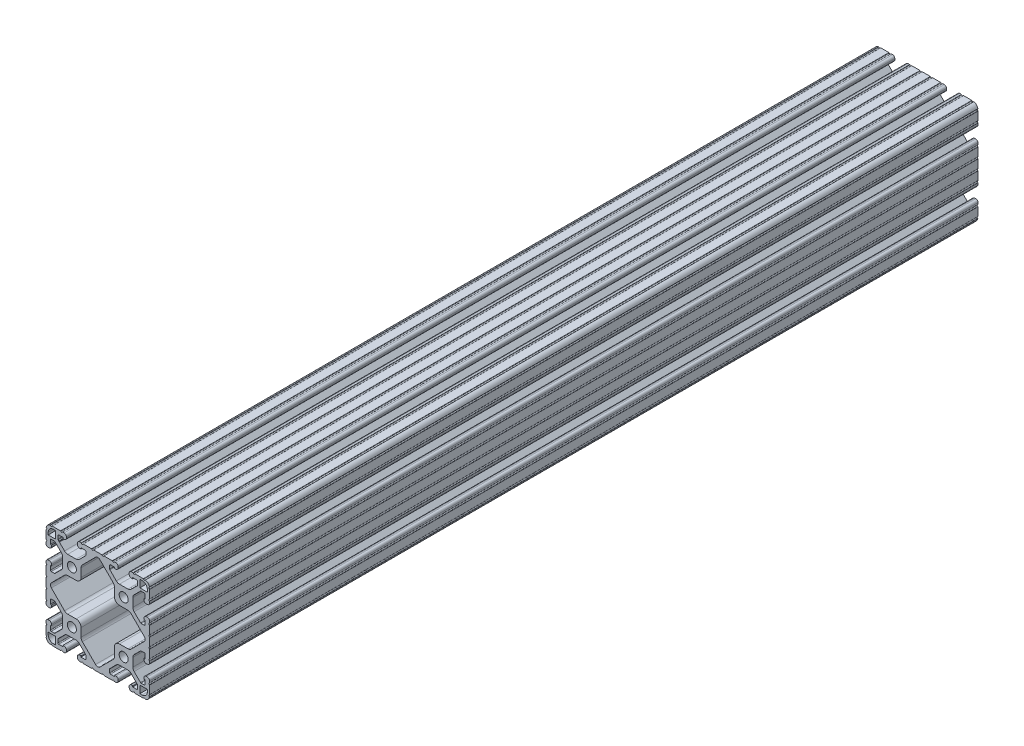
SolidWorks part; units mm, degrees
ref_plane "Front Plane" through (0, 0, 0) normal (0, 0, 1) x (1, 0, 0)
ref_plane "Top Plane" through (0, 0, 0) normal (0, 1, 0) x (1, 0, 0)
ref_plane "Right Plane" through (0, 0, 0) normal (1, 0, 0) x (0, 0, -1)
sketch "Sketch2" plane through (0, 0, 0) normal (0, 0, 1) x (1, 0, 0)
  line L0 (19.05, 38.1) -> (19.05, -38.1) construction
  line L1 (-38.1, 0) -> (38.1, 0) construction
  line L2 (23.114, -38.1) -> (38.1, -38.1)
  line L3 (38.1, -38.1) -> (38.1, -23.114)
  line L5 (25.6858, -34.8488) -> (28.7274, -34.8488)
  line L7 (19.05, -19.05) -> (38.1, -38.1) construction
  line L9 (34.8488, -25.6857) -> (34.8488, -28.7274)
  line L11 (28.7212, -26.4222) -> (26.4222, -28.7212) construction
  line L12 (29.337, -34.2392) -> (29.337, -31.6359)
  line L13 (23.5075, -25.8064) -> (29.337, -31.6359)
  line L14 (34.2392, -29.337) -> (31.6359, -29.337)
  line L15 (25.8064, -23.5075) -> (31.6359, -29.337)
  line L16 (23.114, -38.1) -> (23.114, -34.036)
  line L18 (23.114, -34.036) -> (25.6858, -34.036)
  line L19 (25.6858, -34.036) -> (25.6858, -34.8488)
  line L20 (38.1, -23.114) -> (34.036, -23.114)
  line L21 (34.036, -23.114) -> (34.036, -25.6858)
  line L22 (34.036, -25.6858) -> (34.8488, -25.6857)
  line L23 (25.6858, -34.8488) -> (25.6858, -38.1) construction
  line L24 (0, 38.1) -> (0, -38.1) construction
  circle A0 centre (19.05, -19.05) radius 3.3274
  arc A1 (28.7274, -34.8488) -> (29.337, -34.2392) centre (28.7274, -34.2392) ccw
  arc A2 (34.8488, -28.7274) -> (34.2392, -29.337) centre (34.2392, -28.7274) cw
  point P8 (19.05, -25.8064)
  point P16 (27.5717, -27.5717)
  dimension "Center Hole Diameter" = 6.6548
  dimension "D3" = 0.6096
  dimension "T-Slot Width" = 8.128
  dimension "T-Slot Depth" = 12.2936
  dimension "Inner Slot Width" = 20.574
  dimension "D1" = 2.5718
  dimension "D2" = 4.064
  dimension "D4" = 0.8128
  dimension "D5" = 45
  dimension "Rail Height" = 76.2
  dimension "D6" = 38.1
  dimension "Rail Width" = 76.2
sketch "Sketch3" plane through (0, 0, 0) normal (1, 0, 0) x (0, 0, -1)
  line L0 (-304.8, -38.1) -> (304.8, -38.1) construction
  line L1 (-266.7, 0) -> (266.7, 0) construction
  dimension "Length" = 609.6
  dimension "D1" = 38.1
sketch "Sketch4" plane through (0, 0, 0) normal (0, 0, 1) x (1, 0, 0)
  line L1 (38.1, -34.29) -> (38.1, -24.7396)
  line L2 (38.1, -23.114) -> (34.036, -23.114) construction
  line L3 (34.036, -23.114) -> (34.036, -25.6858) construction
  line L7 (35.6616, -23.114) -> (36.4744, -23.114)
  line L9 (34.036, -24.7396) -> (34.036, -25.6858)
  line L10 (34.036, -25.6858) -> (34.8488, -25.6857)
  line L11 (34.8488, -25.6857) -> (34.8488, -28.7274)
  line L13 (34.2392, -29.337) -> (31.8885, -29.337)
  line L18 (34.2392, -29.337) -> (31.6359, -29.337) construction
  line L20 (25.8064, -23.5075) -> (31.6359, -29.337) construction
  line L22 (23.114, -38.1) -> (38.1, -38.1) construction
  line L23 (38.1, -38.1) -> (38.1, -23.114) construction
  line L24 (34.29, -38.1) -> (24.7396, -38.1)
  line L25 (23.114, -35.6616) -> (23.114, -36.4744)
  line L26 (23.114, -38.1) -> (23.114, -34.036) construction
  line L27 (23.114, -34.036) -> (25.6858, -34.036) construction
  line L28 (24.7396, -34.036) -> (25.6858, -34.036)
  line L29 (25.6858, -34.036) -> (25.6858, -34.8488)
  line L30 (25.6858, -34.8488) -> (28.7274, -34.8488)
  line L31 (23.5075, -25.8064) -> (29.337, -31.6359) construction
  line L32 (29.337, -34.2392) -> (29.337, -31.6359) construction
  line L33 (29.337, -31.8885) -> (29.337, -34.2392)
  line L35 (24.4597, -26.7587) -> (29.1585, -31.4574)
  line L36 (31.4574, -29.1585) -> (26.7587, -24.4597)
  line L37 (25.8064, -19.05) -> (25.8064, -22.1608)
  line L38 (19.05, -25.8064) -> (19.05, -22.3774)
  line L39 (32.6644, -36.4744) -> (30.9626, -36.4744)
  line L40 (30.9626, -36.4744) -> (30.9626, -30.9626)
  line L41 (36.4744, -30.9626) -> (36.4744, -32.6644)
  line L42 (30.9626, -30.9626) -> (36.4744, -30.9626)
  line L43 (19.05, -19.05) -> (38.1, -38.1) construction
  line L44 (30.9626, -36.4744) -> (30.9626, -38.1) construction
  line L45 (29.337, -33.0638) -> (30.9626, -33.0638) construction
  line L50 (19.05, 38.1) -> (19.05, -38.1) construction
  line L52 (19.05, -25.8064) -> (22.1608, -25.8064)
  line L53 (25.8064, -19.05) -> (22.3774, -19.05)
  arc A12 (34.29, -38.1) -> (38.1, -34.29) centre (34.29, -34.29) ccw
  arc A15 (28.7274, -34.8488) -> (29.337, -34.2392) centre (28.7274, -34.2392) ccw construction
  arc A16 (28.7274, -34.8488) -> (29.337, -34.2392) centre (28.7274, -34.2392) ccw
  arc A19 (34.2392, -29.337) -> (34.8488, -28.7274) centre (34.2392, -28.7274) ccw construction
  arc A20 (34.2392, -29.337) -> (34.8488, -28.7274) centre (34.2392, -28.7274) ccw
  arc A22 (25.8064, -22.1608) -> (26.7587, -24.4597) centre (29.0576, -22.1608) ccw
  arc A23 (36.4744, -32.6644) -> (32.6644, -36.4744) centre (32.6644, -32.6644) cw
  arc A24 (24.4597, -26.7587) -> (22.1608, -25.8064) centre (22.1608, -29.0576) ccw
  arc A26 (31.8885, -29.337) -> (31.4574, -29.1585) centre (31.8885, -28.7274) cw
  arc A27 (23.114, -36.4744) -> (24.7396, -38.1) centre (24.7396, -36.4744) ccw
  arc A28 (23.114, -35.6616) -> (24.7396, -34.036) centre (24.7396, -35.6616) cw
  arc A29 (34.036, -24.7396) -> (35.6616, -23.114) centre (35.6616, -24.7396) cw
  arc A30 (36.4744, -23.114) -> (38.1, -24.7396) centre (36.4744, -24.7396) cw
  arc A31 (29.1585, -31.4574) -> (29.337, -31.8885) centre (28.7274, -31.8885) cw
  circle A32 centre (19.05, -19.05) radius 3.3274 construction
  arc A33 (19.05, -22.3774) -> (22.3774, -19.05) centre (19.05, -19.05) ccw
  point P74 (23.114, -36.068)
  dimension "D2" = 3.2512
  dimension "D1" = 1.6256
  dimension "D3" = 3.81
  dimension "D4" = 3.81
extrude "Boss-Extrude1" add sketch "Sketch4" along normal mid plane 609.6
sketch "Sketch6" plane through (0, 0, 0) normal (0, 0, 1) x (1, 0, 0)
  line L0 (19.05, -19.05) -> (19.05, -38.1) construction
  line L1 (23.114, -35.6616) -> (23.114, -36.4744) construction
  line L2 (24.7396, -34.036) -> (25.6858, -34.036) construction
  line L3 (25.6858, -34.036) -> (25.6858, -34.8488) construction
  line L4 (25.6858, -34.8488) -> (28.7274, -34.8488) construction
  line L5 (29.337, -31.8885) -> (29.337, -34.2392) construction
  line L6 (24.4597, -26.7587) -> (29.1585, -31.4574) construction
  line L7 (23.114, -35.6616) -> (23.114, -36.4744) construction
  line L8 (24.7396, -34.036) -> (25.6858, -34.036) construction
  line L9 (25.6858, -34.036) -> (25.6858, -34.8488) construction
  line L10 (25.6858, -34.8488) -> (28.7274, -34.8488) construction
  line L11 (29.337, -31.8885) -> (29.337, -34.2392) construction
  line L12 (24.4597, -26.7587) -> (29.1585, -31.4574) construction
  line L13 (13.6403, -26.7587) -> (8.9415, -31.4574)
  line L14 (8.763, -31.8885) -> (8.763, -34.2392)
  line L15 (12.4143, -34.8488) -> (9.3726, -34.8488)
  line L16 (12.4143, -34.036) -> (12.4143, -34.8488)
  line L17 (13.3604, -34.036) -> (12.4143, -34.036)
  line L18 (14.986, -35.6616) -> (14.986, -36.4744)
  line L19 (13.3604, -38.1) -> (0, -38.1)
  line L20 (0, -38.1) -> (0, -34.8488)
  line L21 (0, 38.1) -> (0, -38.1) construction
  line L22 (1.6256, -34.1755) -> (11.3413, -24.4597)
  line L23 (12.2936, -22.1608) -> (12.2936, -15.9392)
  line L24 (15.9392, -25.8064) -> (19.05, -25.8064)
  line L25 (12.2936, -19.05) -> (15.7226, -19.05) construction
  line L26 (25.8064, -19.05) -> (22.3774, -19.05) construction
  line L27 (11.2909, -29.108) -> (8.992, -26.8091) construction
  line L28 (28.7212, -26.4222) -> (26.4222, -28.7212) construction
  line L29 (19.05, -19.05) -> (38.1, -38.1) construction
  line L30 (22.1608, -12.2936) -> (15.9392, -12.2936)
  line L31 (34.1755, -1.6256) -> (24.4597, -11.3413)
  line L32 (38.1, 0) -> (34.8488, 0)
  line L33 (38.1, -13.3604) -> (38.1, 0)
  line L34 (35.6616, -14.986) -> (36.4744, -14.986)
  line L35 (34.036, -13.3604) -> (34.036, -12.4143)
  line L36 (34.036, -12.4143) -> (34.8488, -12.4143)
  line L37 (34.8488, -12.4143) -> (34.8488, -9.3726)
  line L38 (31.8885, -8.763) -> (34.2392, -8.763)
  line L39 (26.7587, -13.6403) -> (31.4574, -8.9415)
  line L40 (25.8064, -15.9392) -> (25.8064, -19.05)
  line L41 (19.05, -25.8064) -> (19.05, -22.3774)
  line L42 (22.3774, -19.05) -> (25.8064, -19.05)
  arc A0 (23.114, -36.4744) -> (24.7396, -38.1) centre (24.7396, -36.4744) ccw construction
  arc A1 (24.7396, -34.036) -> (23.114, -35.6616) centre (24.7396, -35.6616) ccw construction
  arc A2 (28.7274, -34.8488) -> (29.337, -34.2392) centre (28.7274, -34.2392) ccw construction
  arc A3 (29.337, -31.8885) -> (29.1585, -31.4574) centre (28.7274, -31.8885) ccw construction
  arc A4 (24.4597, -26.7587) -> (22.1608, -25.8064) centre (22.1608, -29.0576) ccw construction
  arc A5 (23.114, -36.4744) -> (24.7396, -38.1) centre (24.7396, -36.4744) ccw construction
  arc A6 (24.7396, -34.036) -> (23.114, -35.6616) centre (24.7396, -35.6616) ccw construction
  arc A7 (28.7274, -34.8488) -> (29.337, -34.2392) centre (28.7274, -34.2392) ccw construction
  arc A8 (29.337, -31.8885) -> (29.1585, -31.4574) centre (28.7274, -31.8885) ccw construction
  arc A9 (24.4597, -26.7587) -> (22.1608, -25.8064) centre (22.1608, -29.0576) ccw construction
  arc A10 (13.6403, -26.7587) -> (15.9392, -25.8064) centre (15.9392, -29.0576) cw
  arc A11 (8.763, -31.8885) -> (8.9415, -31.4574) centre (9.3726, -31.8885) cw
  arc A12 (9.3726, -34.8488) -> (8.763, -34.2392) centre (9.3726, -34.2392) cw
  arc A13 (13.3604, -34.036) -> (14.986, -35.6616) centre (13.3604, -35.6616) cw
  arc A14 (14.986, -36.4744) -> (13.3604, -38.1) centre (13.3604, -36.4744) cw
  arc A15 (0, -34.8488) -> (1.6256, -34.1755) centre (0, -32.5499) ccw
  arc A16 (11.3413, -24.4597) -> (12.2936, -22.1608) centre (9.0424, -22.1608) ccw
  circle A17 centre (19.05, -19.05) radius 3.3274 construction
  arc A18 (24.4597, -11.3413) -> (22.1608, -12.2936) centre (22.1608, -9.0424) cw
  arc A19 (34.8488, 0) -> (34.1755, -1.6256) centre (32.5499, 0) cw
  arc A20 (36.4744, -14.986) -> (38.1, -13.3604) centre (36.4744, -13.3604) ccw
  arc A21 (34.036, -13.3604) -> (35.6616, -14.986) centre (35.6616, -13.3604) ccw
  arc A22 (34.8488, -9.3726) -> (34.2392, -8.763) centre (34.2392, -9.3726) ccw
  arc A23 (31.8885, -8.763) -> (31.4574, -8.9415) centre (31.8885, -9.3726) ccw
  arc A24 (26.7587, -13.6403) -> (25.8064, -15.9392) centre (29.0576, -15.9392) ccw
  arc A25 (12.2936, -15.9392) -> (15.9392, -12.2936) centre (15.9392, -15.9392) cw
  arc A26 (19.05, -22.3774) -> (22.3774, -19.05) centre (19.05, -19.05) cw
extrude "Boss-Extrude3" add sketch "Sketch6" along normal mid plane 609.6
sketch "Sketch8" plane through (0, 0, 304.8) normal (0, 0, 1) x (1, 0, 0)
  line L0 (38.1, -34.29) -> (38.1, -26.67) construction
  line L1 (38.1, -38.1) -> (38.1, -23.114) construction
  line L2 (38.1, -26.67) -> (38.1, -19.05) construction
  line L3 (38.1, -19.05) -> (38.1, -11.43) construction
  line L4 (38.1, -11.43) -> (38.1, -3.81) construction
  line L5 (38.1, -3.81) -> (38.1, 3.81) construction
  line L6 (38.1, 3.81) -> (38.1, 11.43) construction
  line L7 (38.1, 11.43) -> (38.1, 19.05) construction
  line L8 (38.1, 19.05) -> (38.1, 26.67) construction
  line L9 (38.1, 26.67) -> (38.1, 34.29) construction
  line L10 (19.05, -19.05) -> (38.1, -38.1) construction
  line L11 (38.1, -13.3604) -> (38.1, 0) construction
  line L12 (19.05, -19.05) -> (38.1, -19.05) construction
  circle A0 centre (38.1, -34.29) radius 0.5715
  circle A1 centre (38.1, -26.67) radius 0.5715
  circle A2 centre (38.1, -11.43) radius 0.5715
  circle A3 centre (38.1, -3.81) radius 0.5715
  circle A4 centre (34.29, -38.1) radius 0.5715
  circle A5 centre (26.67, -38.1) radius 0.5715
  circle A6 centre (11.43, -38.1) radius 0.5715
  circle A7 centre (3.81, -38.1) radius 0.5715
  dimension "D1" = 1.143
extrude "Cut-Extrude2" cut sketch "Sketch8" against normal through all
fillet "Fillet1" radius 0.254 16 edges at (3.2385, -38.1, 0) (4.3815, -38.1, 0) (10.8585, -38.1, 0) (12.0015, -38.1, 0) (26.0985, -38.1, 0) (27.2415, -38.1, 0) (33.7185, -38.1, 0) (34.8599, -38.0571, 0) (38.0571, -34.8599, 0) (38.1, -33.7185, 0) (38.1, -27.2415, 0) (38.1, -26.0985, 0) (38.1, -12.0015, 0) (38.1, -10.8585, 0) (38.1, -3.2385, 0) (38.1, -4.3815, 0)
mirror "Mirror3" about plane through (0, 0, 0) normal (0, 1, 0) of bodies 144 134
mirror "Mirror6" about plane through (0, 0, 0) normal (1, 0, 0) of bodies 137 140
sketch "Sketch7" plane through (0, 0, 0) normal (0, 0, 1) x (1, 0, 0)
  line L0 (-28.6637, 30.9626) -> (-28.6637, 30.5562)
  line L1 (-24.4597, 26.7587) -> (-29.1585, 31.4574) construction
  line L2 (-28.6637, 30.5562) -> (-28.2573, 30.5562)
  line L3 (-28.2573, 30.5562) -> (-28.6637, 30.9626)
  line L4 (-36.4744, 30.9626) -> (-30.9626, 30.9626) construction
  dimension "D1" = 0.4064
extrude "Cut-Extrude1" cut sketch "Sketch7" against normal through all both and the other way through all
equation "\"D3@Sketch2\"=\"T-Slot Width@Sketch2\"*0.075"
equation "\"D1@Boss-Extrude1\"=\"Length@Sketch3\""
equation "\"D1@Sketch2\"=\"Inner Slot Width@Sketch2\"*0.125"
equation "\"D4@Sketch2\"=\"D2@Sketch2\"*0.2"
equation "\"D1@Sketch4\"=\"D2@Sketch2\"*0.4"
equation "\"D3@Sketch4\"=\"Rail Width@Sketch2\" * 0.05"
equation "\"D4@Sketch4\"=\"Rail Width@Sketch2\" * 0.05"
equation "\"D2@Sketch4\"=\"D1@Sketch4\"*2"
equation "\"D1@Boss-Extrude3\"=\"Length@Sketch3\""
equation "\"D1@Sketch7\"=\"D4@Sketch2\"*0.5"
equation "\"D1@Sketch8\"=\"Rail Width@Sketch2\"*.015"
